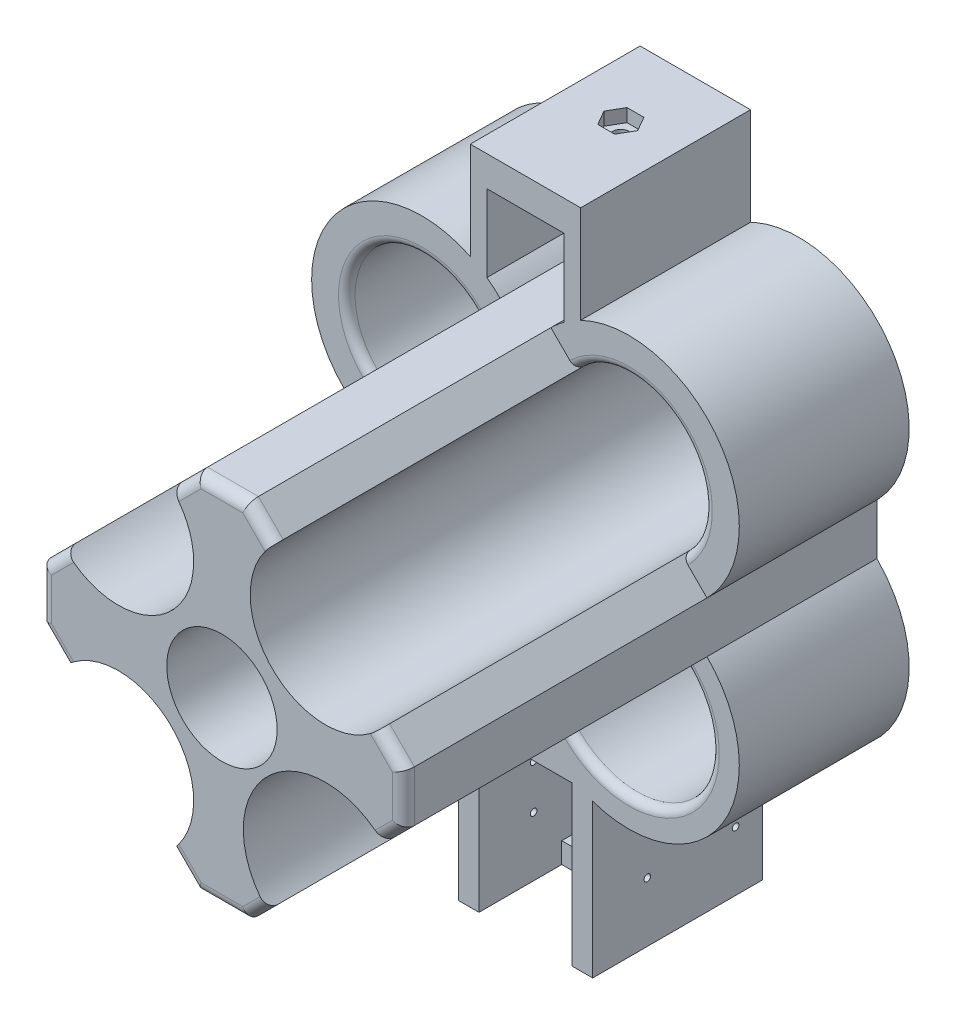
SolidWorks part; units mm, degrees
ref_plane "정면" through (0, 0, 0) normal (0, 0, 1) x (1, 0, 0)
ref_plane "윗면" through (0, 0, 0) normal (0, 1, 0) x (1, 0, 0)
ref_plane "우측면" through (0, 0, 0) normal (1, 0, 0) x (0, 0, -1)
sketch "스케치1" plane through (0, 0, 0) normal (0, 0, 1) x (1, 0, 0)
  line L0 (0, 72.5463) -> (0, -72.2944) construction
  line L1 (-104.379, 0) -> (115.275, 0) construction
  circle A0 centre (-37.5, 37.5) radius 27
  circle A1 centre (37.5, 37.5) radius 27
  circle A2 centre (-37.5, -37.5) radius 27
  arc A5 (0, 51.4194) -> (51.4194, 0) centre (37.5, 37.5) cw
  arc A6 (51.4194, 0) -> (0, -51.4194) centre (37.5, -37.5) cw
  arc A7 (0, -51.4194) -> (-51.4194, 0) centre (-37.5, -37.5) cw
  circle A8 centre (37.5, -37.5) radius 29.5
  arc A9 (0, 51.4194) -> (-51.4194, 0) centre (-37.5, 37.5) ccw
  dimension "D1" = 54
  dimension "D4" = 59
  dimension "D2" = 75
  dimension "D3" = 75
  dimension "D5" = 75
  dimension "D6" = 75
extrude "보스-돌출1" add sketch "스케치1" against normal blind 50 contours A8 A1 A0 A2 region at (-1.5248, 1.5248, 0)
sketch "스케치2" plane through (0, 0, 0) normal (0, 0, 1) x (1, 0, 0)
  line L0 (0, 72.5463) -> (0, -72.2944) construction
  line L1 (-104.379, 0) -> (115.275, 0) construction
  line L2 (0, 0) -> (-43.949, 43.949) construction
  line L3 (0, 0) -> (45.7617, 45.7617) construction
  line L4 (0, 0) -> (-43.949, -43.949) construction
  line L5 (0, 0) -> (45.7617, -45.7617) construction
  line L6 (-18.4081, 56.5919) -> (-9.2157, 65.7843)
  line L7 (-9.2157, 65.7843) -> (-18.4081, 56.5919)
  line L8 (18.4081, 56.5919) -> (9.2157, 65.7843)
  line L9 (9.2157, 65.7843) -> (18.4081, 56.5919)
  line L10 (-56.5919, -18.4081) -> (-65.7843, -9.2157)
  line L11 (-65.7843, -9.2157) -> (-56.5919, -18.4081)
  line L12 (58.3597, -16.6403) -> (65.7843, -9.2157)
  line L13 (65.7843, -9.2157) -> (58.3597, -16.6403)
  line L14 (-56.5919, 18.4081) -> (-65.7843, 9.2157)
  line L15 (56.5919, 18.4081) -> (65.7843, 9.2157)
  line L16 (-18.4081, -56.5919) -> (-9.2157, -65.7843)
  line L17 (16.6403, -58.3597) -> (9.2157, -65.7843)
  arc A0 (-56.5919, 18.4081) -> (-18.4081, 56.5919) centre (-37.5, 37.5) ccw
  arc A1 (56.5919, 18.4081) -> (18.4081, 56.5919) centre (37.5, 37.5) cw
  arc A2 (-56.5919, -18.4081) -> (-18.4081, -56.5919) centre (-37.5, -37.5) cw
  arc A5 (0, 51.4194) -> (9.2157, 65.7843) centre (37.5, 37.5) cw
  arc A6 (51.4194, 0) -> (65.7843, -9.2157) centre (37.5, -37.5) cw
  arc A7 (0, -51.4194) -> (-9.2157, -65.7843) centre (-37.5, -37.5) cw
  arc A8 (58.3597, -16.6403) -> (16.6403, -58.3597) centre (37.5, -37.5) ccw
  arc A9 (0, 51.4194) -> (-9.2157, 65.7843) centre (-37.5, 37.5) ccw
  arc A10 (-65.7843, 9.2157) -> (-51.4194, 0) centre (-37.5, 37.5) ccw
  arc A11 (65.7843, 9.2157) -> (51.4194, 0) centre (37.5, 37.5) cw
  arc A12 (-65.7843, -9.2157) -> (-51.4194, 0) centre (-37.5, -37.5) cw
  arc A13 (9.2157, -65.7843) -> (0, -51.4194) centre (37.5, -37.5) cw
  dimension "D1" = 54
  dimension "D4" = 59
  dimension "D2" = 75
  dimension "D3" = 75
  dimension "D5" = 75
  dimension "D6" = 75
extrude "보스-돌출2" add sketch "스케치2" along normal blind 110 contours A13 L17 A8 L12 A6 A11 L15 A1 L8 A5 A9 L6 A0 L14 A10 A12 L10 A2 L16 A7 region at (-0.9708, 0.9708, 0)
sketch "스케치3" plane through (0, 0, 110) normal (0, 0, 1) x (1, 0, 0)
  circle A0 centre (0, 0) radius 20
  dimension "D1" = 40
extrude "컷-돌출1" cut sketch "스케치3" against normal blind 70
ref_plane "평면1" through (0, 37.5, 0) normal (0, 1, 0) x (1, 0, 0)
sketch "스케치4" plane through (0, 37.5, 0) normal (0, 1, 0) x (1, 0, 0)
  line L0 (-57, 61.5647) -> (-77.5, 61.5647)
  line L2 (-64.5, 50) -> (-44, 61.5647)
  line L4 (-77.5, 61.5647) -> (-77.5, 50)
  line L8 (-44, 61.5647) -> (-57, 61.5647)
  line L9 (-77.5, 50) -> (-64.5, 50)
  line L10 (-37.5, 65.2315) -> (-37.5, 113.4323) construction
  dimension "D2" = 31
sketch "스케치5" plane through (0, 37.5, 0) normal (0, 1, 0) x (1, 0, 0)
  line L0 (37.5, 80.5871) -> (37.5, 65.2315) construction
  line L4 (0, 54.9669) -> (0, 101.8932) construction
  line L6 (44, 61.5647) -> (57, 61.5647)
  line L7 (57, 61.5647) -> (77.5, 61.5647)
  line L8 (77.5, 61.5647) -> (77.5, 50)
  line L10 (64.5, 50) -> (44, 61.5647)
  line L12 (64.5, 50) -> (77.5, 50)
  line L13 (37.5, 50) -> (37.5, 43.0011) construction
revolve "회전1" add sketch "스케치4" angle 360 about L10
revolve "회전2" add sketch "스케치5" angle 360 about L13
ref_plane "평면2" through (0, -37.5, 0) normal (0, 1, 0) x (1, 0, 0)
sketch "스케치6" plane through (0, -37.5, 0) normal (0, 1, 0) x (1, 0, 0)
  line L0 (-57, 61.5647) -> (-77.5, 61.5647)
  line L2 (-64.5, 50) -> (-44, 61.5647)
  line L4 (-77.5, 61.5647) -> (-77.5, 50)
  line L8 (-44, 61.5647) -> (-57, 61.5647)
  line L9 (-77.5, 50) -> (-64.5, 50)
  line L10 (-37.5, 65.2315) -> (-37.5, 113.4323) construction
  dimension "D2" = 31
revolve "회전3" add sketch "스케치6" angle 360 about L10
sketch "스케치7" plane through (0, -37.5, 0) normal (0, 1, 0) x (1, 0, 0)
  line L0 (46.75, 60.1526) -> (46.75, 61.5647)
  line L3 (46.75, 60.1526) -> (67, 50)
  line L4 (77.5, 61.5647) -> (0, 61.5647) construction
  line L5 (46.75, 61.5647) -> (77.5, 61.5647)
  line L8 (67, 50) -> (77.5, 50)
  line L9 (37.5, 64.7902) -> (37.5, 77.3625) construction
  line L10 (77.5, 61.5647) -> (77.5, 50)
  dimension "D2" = 33
revolve "회전4" add sketch "스케치7" angle 360 about L9
ref_plane "평면3" through (0, 0, -50) normal (0, 0, 1) x (1, 0, 0)
ref_plane "평면4" through (0, 0, 110) normal (0, 0, 1) x (1, 0, 0)
sketch "스케치22" plane through (0, 0, 110) normal (0, 0, 1) x (1, 0, 0)
  line L0 (0, 72.5463) -> (0, -72.2944) construction
  line L1 (-104.379, 0) -> (51.4194, 0) construction
  line L2 (0, 0) -> (-43.949, 43.949) construction
  line L3 (0, 0) -> (45.7617, 45.7617) construction
  line L4 (0, 0) -> (-43.949, -43.949) construction
  line L5 (0, 0) -> (45.7617, -45.7617) construction
  line L6 (-18.0546, 56.9454) -> (-9.2157, 65.7843)
  line L7 (-9.2157, 65.7843) -> (-18.0546, 56.9454)
  line L8 (18.0546, 56.9454) -> (9.2157, 65.7843)
  line L9 (9.2157, 65.7843) -> (18.0546, 56.9454)
  line L10 (-56.9454, -18.0546) -> (-65.7843, -9.2157)
  line L11 (-65.7843, -9.2157) -> (-56.9454, -18.0546)
  line L12 (58.89, -16.11) -> (65.7843, -9.2157)
  line L13 (65.7843, -9.2157) -> (58.89, -16.11)
  line L14 (-56.9454, 18.0546) -> (-65.7843, 9.2157)
  line L15 (56.9454, 18.0546) -> (65.7843, 9.2157)
  line L16 (-18.0546, -56.9454) -> (-9.2157, -65.7843)
  line L17 (16.11, -58.89) -> (9.2157, -65.7843)
  line L18 (65.7843, 9.2157) -> (65.7843, -9.2157)
  line L19 (-9.2157, 65.7843) -> (9.2157, 65.7843)
  line L20 (-65.7843, 9.2157) -> (-65.7843, -9.2157)
  line L21 (-9.2157, -65.7843) -> (9.2157, -65.7843)
  arc A0 (-56.9454, 18.0546) -> (-18.0546, 56.9454) centre (-37.5, 37.5) ccw
  arc A1 (56.9454, 18.0546) -> (18.0546, 56.9454) centre (37.5, 37.5) cw
  arc A2 (-56.9454, -18.0546) -> (-18.0546, -56.9454) centre (-37.5, -37.5) cw
  arc A8 (58.89, -16.11) -> (16.11, -58.89) centre (37.5, -37.5) ccw
  circle A11 centre (0, 0) radius 20
  dimension "D1" = 55
  dimension "D4" = 60.5
  dimension "D2" = 75
  dimension "D3" = 75
  dimension "D5" = 75
  dimension "D6" = 75
extrude "보스-돌출6" add sketch "스케치22" against normal blind 171.56 contours A8 L12 L18 L15 A1 L8 L19 L6 A0 L14 L20 L10 A2 L16 L21 L17 A11 region at (-12.3195, 60.0492, 110)
fillet "필렛1" radius 4 12 edges at (-61.1881, -13.8119, 110) (-61.1881, 13.8119, 110) (-13.8119, 61.1881, 110) (13.8119, 61.1881, 110) (61.1881, 13.8119, 110) (62.072, -12.928, 110) (12.928, -62.072, 110) (-13.8119, -61.1881, 110) (-65.7843, 0, 110) (0, 65.7843, 110) (65.7843, 0, 110) (0, -65.7843, 110)
ref_plane "평면5" through (0, 0, -61.56) normal (0, 0, 1) x (1, 0, 0)
sketch "스케치26" plane through (0, 0, -61.56) normal (0, 0, 1) x (1, 0, 0)
  line L0 (0, 72.5463) -> (0, -72.2944) construction
  line L1 (-104.379, 0) -> (115.275, 0) construction
  line L2 (0, 0) -> (-43.949, 43.949) construction
  line L3 (0, 0) -> (45.7617, 45.7617) construction
  line L4 (0, 0) -> (-43.949, -43.949) construction
  line L5 (0, 0) -> (45.7617, -45.7617) construction
  line L6 (-18.4081, 56.5919) -> (-9.2157, 65.7843)
  line L7 (-9.2157, 65.7843) -> (-18.4081, 56.5919)
  line L8 (18.4081, 56.5919) -> (9.2157, 65.7843)
  line L9 (9.2157, 65.7843) -> (18.4081, 56.5919)
  line L10 (-56.5919, -18.4081) -> (-65.7843, -9.2157)
  line L11 (-65.7843, -9.2157) -> (-56.5919, -18.4081)
  line L12 (58.3597, -16.6403) -> (65.7843, -9.2157)
  line L13 (65.7843, -9.2157) -> (58.3597, -16.6403)
  line L14 (-56.5919, 18.4081) -> (-65.7843, 9.2157)
  line L15 (56.5919, 18.4081) -> (65.7843, 9.2157)
  line L16 (-18.4081, -56.5919) -> (-9.2157, -65.7843)
  line L17 (16.6403, -58.3597) -> (9.2157, -65.7843)
  arc A0 (-56.5919, 18.4081) -> (-18.4081, 56.5919) centre (-37.5, 37.5) ccw
  arc A1 (56.5919, 18.4081) -> (18.4081, 56.5919) centre (37.5, 37.5) cw
  arc A2 (-56.5919, -18.4081) -> (-18.4081, -56.5919) centre (-37.5, -37.5) cw
  arc A5 (0, 51.4194) -> (9.2157, 65.7843) centre (37.5, 37.5) cw
  arc A6 (51.4194, 0) -> (65.7843, -9.2157) centre (37.5, -37.5) cw
  arc A7 (0, -51.4194) -> (-9.2157, -65.7843) centre (-37.5, -37.5) cw
  arc A8 (58.3597, -16.6403) -> (16.6403, -58.3597) centre (37.5, -37.5) ccw
  arc A9 (0, 51.4194) -> (-9.2157, 65.7843) centre (-37.5, 37.5) ccw
  arc A10 (-65.7843, 9.2157) -> (-51.4194, 0) centre (-37.5, 37.5) ccw
  arc A11 (65.7843, 9.2157) -> (51.4194, 0) centre (37.5, 37.5) cw
  arc A12 (-65.7843, -9.2157) -> (-51.4194, 0) centre (-37.5, -37.5) cw
  arc A13 (9.2157, -65.7843) -> (0, -51.4194) centre (37.5, -37.5) cw
  dimension "D1" = 54
  dimension "D4" = 59
  dimension "D2" = 75
  dimension "D3" = 75
  dimension "D5" = 75
  dimension "D6" = 75
extrude "보스-돌출8" add sketch "스케치26" along normal blind 50 contours A13 L17 A8 L12 A6 A11 L15 A1 L8 A5 A9 L6 A0 L14 A10 A12 L10 A2 L16 A7 region at (-0.9708, 0.9708, -61.56)
sketch "스케치28" plane through (0, 0, 110) normal (0, 0, 1) x (1, 0, 0)
  line L0 (0, 72.5463) -> (0, -72.2944) construction
  line L1 (-104.379, 0) -> (115.275, 0) construction
  circle A0 centre (-37.5, 37.5) radius 27.25
  circle A1 centre (37.5, 37.5) radius 27.25
  circle A2 centre (-37.5, -37.5) radius 27.25
  circle A8 centre (37.5, -37.5) radius 29.75
  dimension "D1" = 54.5
  dimension "D4" = 59.5
  dimension "D2" = 75
  dimension "D3" = 75
  dimension "D5" = 75
  dimension "D6" = 75
extrude "컷-돌출8" cut sketch "스케치28" against normal blind 160
sketch "스케치36" plane through (0, 0, -61.56) normal (0, 0, 1) x (1, 0, 0)
  line L1 (0, 51.4194) -> (0, 106.3039) construction
  line L2 (20, 108.7843) -> (20, 65.7843)
  line L3 (20, 108.7843) -> (-20, 108.7843)
  line L4 (14, 97.7843) -> (-14, 97.7843)
  line L8 (-20, 108.7843) -> (-20, 65.7843)
  line L9 (-14, 97.7843) -> (-14, 65.7843)
  line L10 (-14, 65.7843) -> (-20, 65.7843)
  line L11 (14, 97.7843) -> (14, 65.7843)
  line L12 (14, 65.7843) -> (20, 65.7843)
  point P10 (0, 97.7843)
  point P15 (0, 108.7843)
  dimension "D1" = 40
  dimension "D2" = 11
  dimension "D3" = 28
extrude "보스-돌출15" add sketch "스케치36" along normal up to vertex (61.56 mm away) up to point (9.2157, 65.7843, 0)
sketch "스케치37" plane through (0, 108.7843, 0) normal (0, 1, 0) x (1, 0, 0)
  line L0 (-37.5563, 61.56) -> (37.5563, 61.56) construction
  circle A0 centre (0, 34.56) radius 2.95
  dimension "D1" = 5.9
  dimension "D2" = 27
extrude "컷-돌출9" cut sketch "스케치37" against normal blind 15
sketch "스케치39" plane through (0, 108.7843, 0) normal (0, 1, 0) x (1, 0, 0)
  line L1 (3.06, 39.86) -> (-3.06, 39.86)
  line L2 (-3.06, 39.86) -> (-6.1199, 34.56)
  line L3 (-6.1199, 34.56) -> (-3.06, 29.26)
  line L4 (-3.06, 29.26) -> (3.06, 29.26)
  line L5 (3.06, 29.26) -> (6.1199, 34.56)
  line L6 (6.1199, 34.56) -> (3.06, 39.86)
  circle A0 centre (0, 34.56) radius 5.3 construction
  dimension "D1" = 10.6
extrude "컷-돌출10" cut sketch "스케치39" against normal blind 4.75
sketch "스케치41" plane through (0, 0, -61.56) normal (0, 0, 1) x (1, 0, 0)
  line L0 (0, -51.4194) -> (0, -134.4155) construction
  line L1 (-16.85, -73.2843) -> (16.85, -73.2843)
  line L2 (-16.85, -73.2843) -> (-16.85, -123.2843)
  line L3 (-16.85, -123.2843) -> (16.85, -123.2843)
  line L4 (16.85, -73.2843) -> (16.85, -123.2843)
  line L5 (-16.85, -73.2843) -> (16.85, -123.2843) construction
  line L6 (-16.85, -123.2843) -> (16.85, -73.2843) construction
  line L8 (-24.35, -65.7843) -> (24.35, -65.7843)
  line L9 (24.35, -65.7843) -> (24.35, -130.7843)
  line L10 (24.35, -130.7843) -> (-24.35, -130.7843)
  line L12 (-24.35, -130.7843) -> (-24.35, -65.7843)
  line L13 (-9.2157, -65.7843) -> (9.2157, -65.7843) construction
  point P0 (0, -98.2843)
  dimension "D1" = 33.7
  dimension "D2" = 50
  dimension "D3" = 7.5
  dimension "D4" = 7.5
  dimension "D5" = 7.5
  dimension "D6" = 7.5
extrude "보스-돌출16" add sketch "스케치41" along normal up to vertex (61.56 mm away) up to point (-9.2157, -65.7843, 0)
sketch "스케치42" plane through (0, 0, -61.5647) normal (0, 0, -1) x (-1, 0, 0)
  line L1 (-16.85, -73.2843) -> (16.85, -73.2843)
  line L2 (-16.85, -73.2843) -> (-16.85, -123.2843)
  line L3 (-16.85, -123.2843) -> (16.85, -123.2843)
  line L4 (16.85, -73.2843) -> (16.85, -123.2843)
  point P0 (0, -98.2843)
  point P9 (0, 0)
  point P17 (0, 0)
  dimension "D1" = 33.7
  dimension "D2" = 50
extrude "보스-돌출17" add sketch "스케치42" against normal blind 3
sketch "스케치43" plane through (0, -130.7843, 0) normal (0, -1, 0) x (1, 0, 0)
  line L0 (-24.35, 0) -> (24.35, 0) construction
  line L1 (-16.85, 0) -> (16.85, 0)
  line L2 (-16.85, 0) -> (-16.85, -30)
  line L3 (-16.85, -30) -> (16.85, -30)
  line L4 (16.85, 0) -> (16.85, -30)
  line L5 (-24.35, 0) -> (-24.35, -61.56) construction
  line L6 (24.35, -61.56) -> (24.35, 0) construction
  dimension "D1" = 7.5
  dimension "D2" = 7.5
  dimension "D3" = 30
extrude "컷-돌출11" cut sketch "스케치43" against normal up to vertex (7.5 mm away) up to point (16.85, -123.2843, 0)
sketch "스케치44" plane through (24.35, 0, 0) normal (1, 0, 0) x (0, 0, -1)
  line L0 (61.56, -130.7843) -> (61.56, -75.2767) construction
  line L1 (0, -130.7843) -> (61.56, -130.7843) construction
  circle A0 centre (51.81, -109.2843) radius 1.2
  circle A1 centre (51.81, -93.2843) radius 1.2
  circle A2 centre (19.81, -109.2843) radius 1.2
  circle A3 centre (19.81, -93.2843) radius 1.2
  point P10 (0, 0)
  point P13 (0, 0)
  dimension "D2" = 2.4
  dimension "D3" = 2.4
  dimension "D7" = 2.4
  dimension "D8" = 2.4
  dimension "D1" = 9.75
  dimension "D4" = 9.75
  dimension "D5" = 16
  dimension "D6" = 21.5
  dimension "D9" = 16
  dimension "D10" = 21.5
  dimension "D11" = 32
  dimension "D12" = 32
extrude "컷-돌출12" cut sketch "스케치44" against normal through all
fillet "필렛2" radius 3 4 edges at (-56.7687, -56.7687, 0) (-56.7687, 56.7687, 0) (56.7687, 56.7687, 0) (58.5364, -58.5364, 0)
